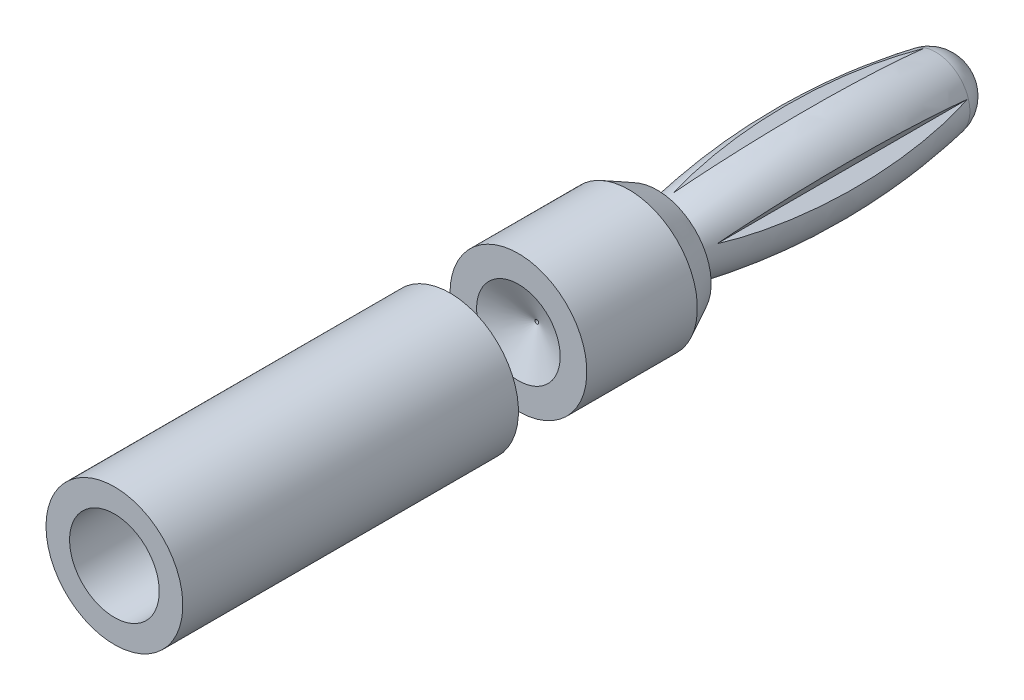
SolidWorks part; units mm, degrees
ref_plane "Front Plane" through (0, 0, 0) normal (1, 0, 0) x (0, 1, 0)
ref_plane "Top Plane" through (0, 0, 0) normal (0, 0, 1) x (0, 1, 0)
ref_plane "Right Plane" through (0, 0, 0) normal (0, 1, 0) x (-1, 0, 0)
sketch "Sketch2" plane through (0, 0, 0) normal (1, 0, 0) x (0, 1, 0)
  line L0 (3.8027, 12.9231) -> (3.8027, -2.4659)
  line L1 (3.8027, -2.4659) -> (4.8827, -2.4659)
  line L2 (4.8827, -2.4659) -> (4.8827, 12.9231)
  line L3 (4.8827, 12.9231) -> (3.8027, 12.9231)
  line L4 (3.8027, -5.6017) -> (5.0227, -5.6017)
  line L10 (6.8517, -11.9636) -> (4.4616, -11.9636)
  line L11 (4.4616, -11.9636) -> (3.8027, -10.671)
  line L12 (3.8027, -10.671) -> (3.8027, -5.6017)
  line L13 (6.9396, 8.7743) -> (6.9396, 17.6034) construction
  line L14 (5.0227, -5.6017) -> (6.8517, -6.446)
  line L15 (6.8517, -6.446) -> (6.8517, -11.9636)
  line L16 (6.8517, -11.9636) -> (6.8517, -25.9636)
  line L17 (5.6129, -11.9636) -> (6.8517, -11.9636)
  arc A0 (6.8517, -25.9636) -> (5.3688, -24.7342) centre (6.8517, -24.4545) cw
  arc A1 (5.6129, -11.9636) -> (5.3688, -24.7342) centre (36.115, -18.9344) ccw
  dimension "D1" = 15.389
  dimension "D2" = 4.1137
  dimension "D3" = 1.22
  dimension "D4" = 1.08
  dimension "D5" = 0.8443
  dimension "D6" = 1.829
  dimension "D7" = 0.6589
  dimension "D8" = 6.3619
  dimension "D9" = 3.1358
  dimension "D10" = 14
revolve "Revolve1" add sketch "Sketch2" angle 360 about L13 region at (0, 4.3427, 5.2286) region at (0, 5.319, -8.8413) region at (0, 5.9563, -18.8715)
sketch "Sketch5" plane through (0, 0, -11.9636) normal (0, 0, -1) x (1, 0, 0)
  line L0 (-0.085, -4.4631) -> (0.4759, -5.4296)
  line L1 (0.4759, -5.4296) -> (1.3987, -4.8941)
  line L2 (2.4765, -6.8546) -> (1.51, -7.4155)
  line L3 (1.51, -7.4155) -> (2.0455, -8.3382)
  line L4 (0.085, -9.4161) -> (-0.4759, -8.4496)
  line L5 (-0.4759, -8.4496) -> (-1.3987, -8.9851)
  line L6 (-2.4765, -7.0246) -> (-1.51, -6.4637)
  line L7 (-1.51, -6.4637) -> (-2.0455, -5.5409)
  circle A0 centre (0, -6.9396) radius 2.478 construction
  arc A1 (-0.085, -4.4631) -> (1.3987, -4.8941) centre (0, -6.9396) cw
  arc A2 (2.4765, -6.8546) -> (2.0455, -8.3382) centre (0, -6.9396) cw
  arc A3 (0.085, -9.4161) -> (-1.3987, -8.9851) centre (0, -6.9396) cw
  arc A4 (-2.4765, -7.0246) -> (-2.0455, -5.5409) centre (0, -6.9396) cw
  dimension "D1" = 4
extrude "Cut-Extrude1" cut sketch "Sketch5" along normal blind 14 contours A1 L1 L0 | L6 L7 A4 | L2 L3 A2 | L4 L5 A3
sketch "Sketch3" plane through (0, 0, -11.9636) normal (0, 0, -1) x (1, 0, 0)
  line L0 (0, -6.9396) -> (1.0989, -4.7186)
  line L1 (1.0989, -4.7186) -> (1.7937, -5.2299)
  line L2 (1.7937, -5.2299) -> (0, -6.9396)
  circle A0 centre (0, -6.9396) radius 2.425
  circle A1 centre (0, -6.9396) radius 2.478 construction
  dimension "D1" = 4.85
ref_plane "Plane1" through (1.3911, 4.1281, -10.671) normal (0.4435, -0.8963, 0) x (-0.8963, -0.4435, 0)
thread "Thread1" pitch 0.7 method extrude profile "Thread Profile2" start angle 0, offset 0, length 6, pitch 0.7, diameter 4.1137
ref_plane "Plane3" through (2.0568, 6.9396, -2.4659) normal (0, -1, 0) x (1, 0, 0)
sketch "Thread Profile2" plane through (2.0568, 6.9396, -2.4659) normal (0, -1, 0) x (1, 0, 0)
  line L0 (0, 0) -> (0, 0.7) construction
  line L11 (0, 0) -> (0, 0.6125)
  line L12 (0, 0.6125) -> (-0.3789, 0.3937)
  line L13 (-0.3789, 0.3937) -> (-0.3789, 0.2187)
  line L15 (-0.3789, 0.2187) -> (0, 0)
  line L17 (-0.3789, 0.3062) -> (0, 0.3062) construction
  point P2 (0, 0)
  dimension "Pitch" = 0.7
  dimension "Profile_Angle" = 60
  dimension "Profile_Land" = 0.175
  dimension "Profile_Height" = 0.3789
